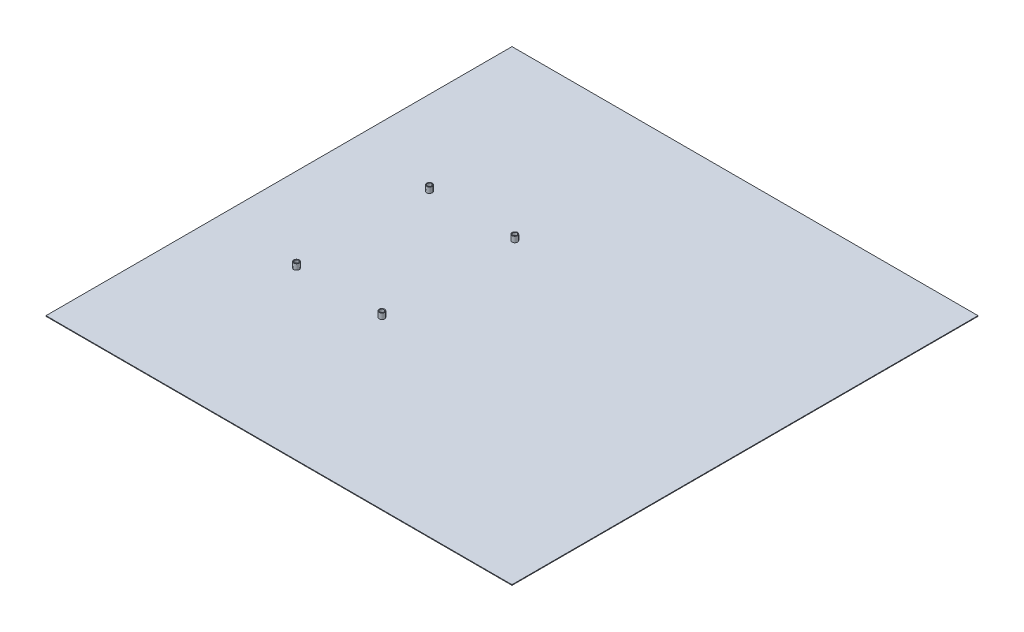
SolidWorks part; units mm, degrees
ref_plane "Front Plane" through (0, 0, 0) normal (0, 0, 1) x (1, 0, 0)
ref_plane "Top Plane" through (0, 0, 0) normal (0, 1, 0) x (1, 0, 0)
ref_plane "Right Plane" through (0, 0, 0) normal (1, 0, 0) x (0, 0, -1)
sketch "Sketch1" plane through (0, 0, 0) normal (0, 1, 0) x (1, 0, 0)
  line L1 (-166.5, -166.5) -> (166.5, -166.5)
  line L2 (-166.5, -166.5) -> (-166.5, 166.5)
  line L3 (-166.5, 166.5) -> (166.5, 166.5)
  line L4 (166.5, -166.5) -> (166.5, 166.5)
  line L5 (-166.5, -166.5) -> (166.5, 166.5) construction
  line L6 (-166.5, 166.5) -> (166.5, -166.5) construction
  point P0 (0, 0)
  dimension "D1" = 333
  dimension "D2" = 333
extrude "Boss-Extrude1" add sketch "Sketch1" along normal blind 0.45
sketch "Sketch2" plane through (0, 0.45, 0) normal (0, 1, 0) x (1, 0, 0)
  line L0 (-166.5, 0) -> (-111.5, 0)
  line L1 (-166.5, 166.5) -> (-166.5, -166.5) construction
  line L3 (-111.5, 52.5) -> (-40.5, 52.5) construction
  line L4 (-111.5, 52.5) -> (-111.5, -52.5) construction
  line L5 (-111.5, -52.5) -> (-40.5, -52.5) construction
  line L6 (-40.5, 52.5) -> (-40.5, -52.5) construction
  line L7 (-111.5, -52.5) -> (-106.5, -52.5) construction
  line L8 (-111.5, -52.5) -> (-111.5, -47.5) construction
  line L9 (-111.5, -47.5) -> (-106.5, -47.5) construction
  line L10 (-106.5, -52.5) -> (-106.5, -47.5) construction
  line L11 (-40.5, -52.5) -> (-45.5, -52.5) construction
  line L12 (-40.5, -52.5) -> (-40.5, -47.5) construction
  line L13 (-40.5, -47.5) -> (-45.5, -47.5) construction
  line L14 (-45.5, -52.5) -> (-45.5, -47.5) construction
  line L15 (-40.5, 52.5) -> (-45.5, 52.5) construction
  line L16 (-40.5, 52.5) -> (-40.5, 47.5) construction
  line L17 (-40.5, 47.5) -> (-45.5, 47.5) construction
  line L18 (-45.5, 52.5) -> (-45.5, 47.5) construction
  line L19 (-111.5, 52.5) -> (-106.5, 52.5) construction
  line L20 (-111.5, 52.5) -> (-111.5, 47.5) construction
  line L21 (-111.5, 47.5) -> (-106.5, 47.5) construction
  line L22 (-106.5, 52.5) -> (-106.5, 47.5) construction
  circle A0 centre (-106.5, -47.5) radius 1.5
  circle A1 centre (-45.5, -47.5) radius 1.5
  circle A2 centre (-45.5, 47.5) radius 1.5
  circle A3 centre (-106.5, 47.5) radius 1.5
  circle A4 centre (-106.5, 47.5) radius 2
  circle A5 centre (-45.5, 47.5) radius 2
  circle A6 centre (-106.5, -47.5) radius 2
  circle A7 centre (-45.5, -47.5) radius 2
  point P9 (-111.5, 0)
  dimension "D12" = 3
  dimension "D13" = 3
  dimension "D14" = 3
  dimension "D15" = 3
  dimension "D16" = 4
  dimension "D17" = 4
  dimension "D18" = 4
  dimension "D19" = 4
  dimension "D1" = 55
  dimension "D2" = 105
  dimension "D3" = 71
  dimension "D4" = 5
  dimension "D5" = 5
  dimension "D6" = 5
  dimension "D7" = 5
  dimension "D8" = 5
  dimension "D9" = 5
  dimension "D10" = 5
  dimension "D11" = 5
extrude "Boss-Extrude4" add sketch "Sketch2" along normal blind 4 contours A5 A2 | A4 A3 | A6 A0 | A7 A1 region at (-108.4434, 0.45, -47.5) region at (-47.4434, 0.45, -47.5) region at (-108.4434, 0.45, 47.5) region at (-47.4434, 0.45, 47.5)
